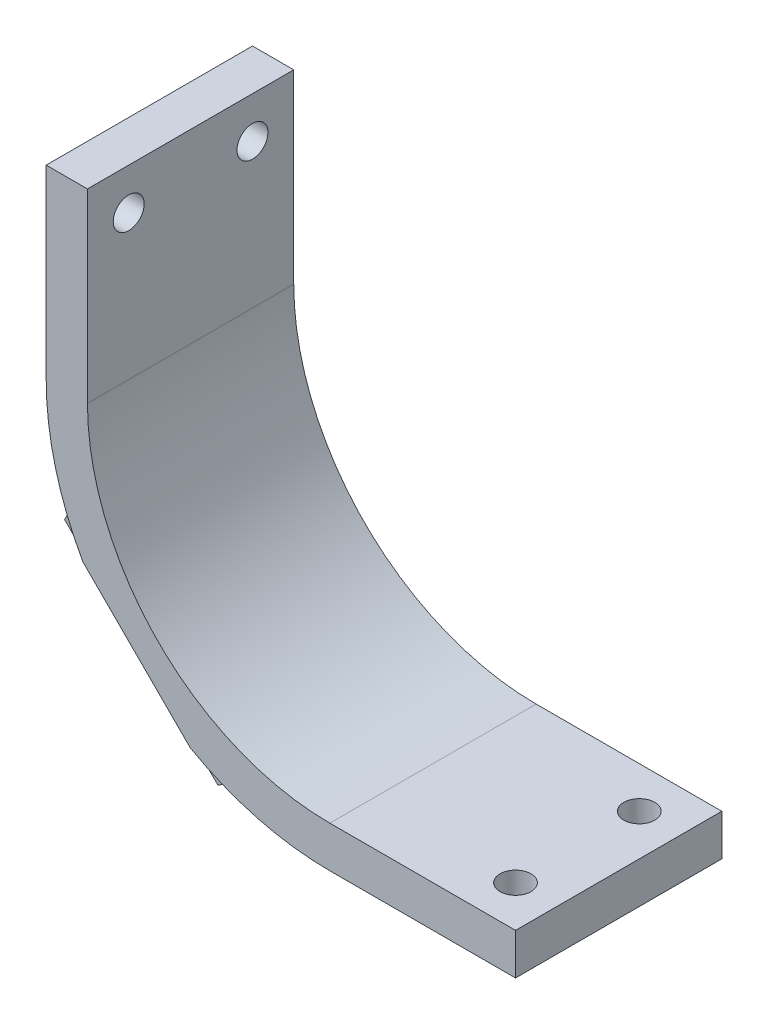
SolidWorks part; units mm, degrees
ref_plane "前视基准面" through (0, 0, 0) normal (0, 0, 1) x (1, 0, 0)
ref_plane "上视基准面" through (0, 0, 0) normal (0, 1, 0) x (1, 0, 0)
ref_plane "右视基准面" through (0, 0, 0) normal (1, 0, 0) x (0, 0, -1)
sketch "草图1" plane through (0, 0, 0) normal (0, 0, 1) x (1, 0, 0)
  line L0 (0, 47) -> (0, 83)
  line L2 (0, 83) -> (-8, 83)
  line L3 (83, 0) -> (83, -8)
  line L4 (-8, 83) -> (-8, 47)
  line L5 (47, -8) -> (83, -8)
  line L6 (47, 0) -> (83, 0)
  arc A0 (0, 47) -> (47, 0) centre (47, 47) ccw
  arc A1 (-8, 47) -> (47, -8) centre (47, 47) ccw
extrude "凸台-拉伸1" add sketch "草图1" along normal blind 40
sketch "草图4" plane through (0, 0, 0) normal (0, 0, -1) x (-1, 0, 0)
  line L4 (6.7401, -36.4386) -> (36.4386, -6.7401)
  line L5 (-47, -8) -> (6.7401, -36.4386)
  line L6 (8, 47) -> (36.4386, -6.7401)
  circle A4 centre (6.7401, -6.7401) radius 11.5
  circle A5 centre (-15.1802, -6.7401) radius 1.8
  circle A6 centre (6.7401, 15.1802) radius 1.8
  circle A7 centre (6.7401, -28.6604) radius 1.8
  circle A8 centre (28.6604, -6.7401) radius 1.8
  arc A9 (-47, -8) -> (8, 47) centre (-47, 47) ccw
extrude "凸台-拉伸3" add sketch "草图4" against normal blind 8
sketch "草图5" plane through (0, 0, 40) normal (0, 0, 1) x (1, 0, 0)
  line L2 (-7.4472, 23.6655) -> (-6.033, 25.0797)
  line L3 (-6.033, 25.0797) -> (25.0797, -6.033)
  line L4 (25.0797, -6.033) -> (23.6655, -7.4472)
  line L5 (-7.4472, 23.6655) -> (-11.8416, 19.2711)
  line L6 (-11.8416, 19.2711) -> (19.2711, -11.8416)
  line L7 (23.6655, -7.4472) -> (19.2711, -11.8416)
chamfer "倒角1" distance 5 angle 45 1 edges at (8.1091, 8.1091, 8)
extrude "切除-拉伸4" cut sketch "草图5" against normal blind 32
sketch "草图6" plane through (0, -8, 0) normal (0, -1, 0) x (1, 0, 0)
  circle A0 centre (75, 8) radius 3
  circle A1 centre (75, 32) radius 3
extrude "切除-拉伸5" cut sketch "草图6" against normal blind 32
sketch "草图7" plane through (-8, 0, 0) normal (-1, 0, 0) x (0, 0, 1)
  circle A0 centre (8, 75) radius 3
  circle A1 centre (32, 75) radius 3
extrude "切除-拉伸6" cut sketch "草图7" against normal blind 32
